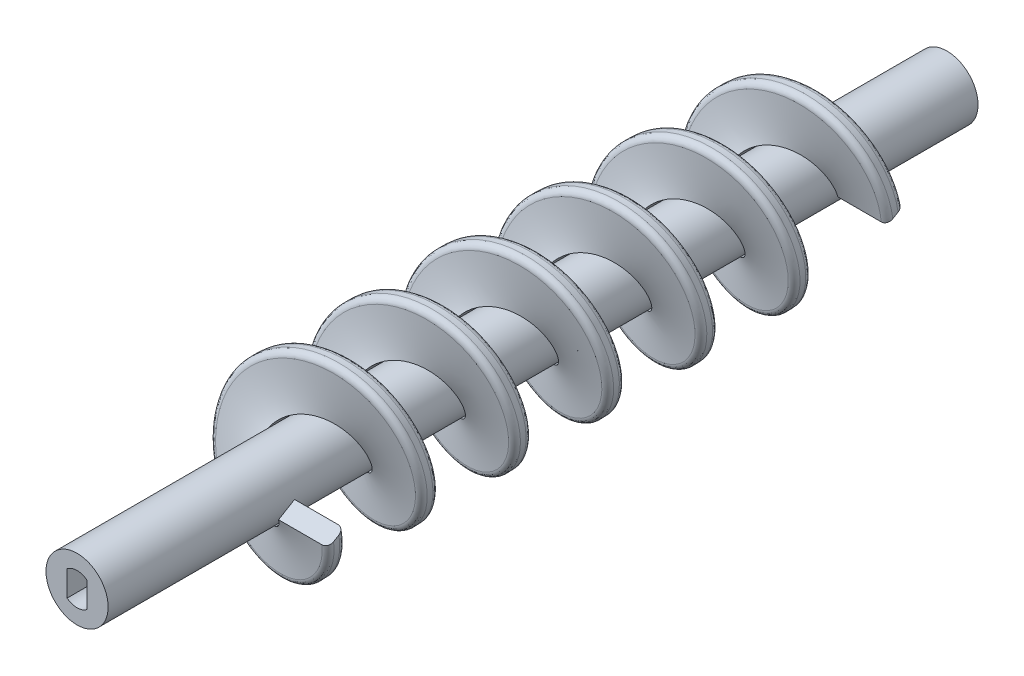
SolidWorks part; units mm, degrees
ref_plane "Front Plane" through (0, 0, 0) normal (0, 0, 1) x (1, 0, 0)
ref_plane "Top Plane" through (0, 0, 0) normal (0, 1, 0) x (1, 0, 0)
ref_plane "Right Plane" through (0, 0, 0) normal (1, 0, 0) x (0, 0, -1)
sketch "Sketch2" plane through (0, 0, 0) normal (0, 0, 1) x (1, 0, 0)
  circle A0 centre (0, 0) radius 5
  dimension "D1" = 10
extrude "Boss-Extrude1" add sketch "Sketch2" along normal mid plane 120
sketch "Sketch3" plane through (0, 0, -60) normal (0, 0, -1) x (-1, 0, 0)
  circle A0 centre (0, 0) radius 4
curve "Helix/Spiral1" pitch 15 height 90 radius 4 centre (0, 0, -60) axis (0, 0, 1) start towards (1, 0, 0)
ref_plane "Plane1" through (4, 0, -60) normal (0, 0.8587, 0.5125) x (1, 0, 0)
sketch "Sketch5" plane through (4, 0, -60) normal (0, 0.8587, 0.5125) x (1, 0, 0)
  line L1 (1, 0) -> (8, 0)
  line L2 (1, 0) -> (1, -3)
  line L3 (1, -3) -> (8, -3)
  line L4 (9, -1) -> (9, -2)
  arc A0 (8, -3) -> (9, -2) centre (8, -2) ccw
  arc A1 (8, 0) -> (9, -1) centre (8, -1) cw
  ellipse E0 centre (-4, 0) end of major axis (-9, 0) minor radius 2.5625 construction
  point P14 (9, 0)
  dimension "D3" = 1
  dimension "D1" = 8
  dimension "D2" = 3
sweep "Sweep1" add profiles "Sketch5" path "Helix/Spiral1"
sketch "Sketch6" plane through (0, 0, 60) normal (0, 0, 1) x (1, 0, 0)
  line L1 (-1.6, -2.0494) -> (1.6, -2.0494)
  line L2 (-1.6, -2.0494) -> (-1.6, 2.0494)
  line L3 (-1.6, 2.0494) -> (1.6, 2.0494)
  line L4 (1.6, -2.0494) -> (1.6, 2.0494)
  line L5 (-1.6, -2.0494) -> (1.6, 2.0494) construction
  line L6 (-1.6, 2.0494) -> (1.6, -2.0494) construction
  circle A0 centre (0, 0) radius 2.6
  dimension "D1" = 5.2
  dimension "D2" = 3.2
extrude "Cut-Extrude1" cut sketch "Sketch6" against normal blind 9 contours L3 A0 | L1 L4 L3 L2 | L1 A0 region at (0, 0, 60) region at (0, -2.2718, 60) region at (0, 2.2718, 60)
sketch "Sketch7" plane through (0, 0, -60) normal (0, 0, -1) x (-1, 0, 0)
  circle A0 centre (0, 0) radius 5
extrude "Boss-Extrude3" add sketch "Sketch7" along normal blind 20
